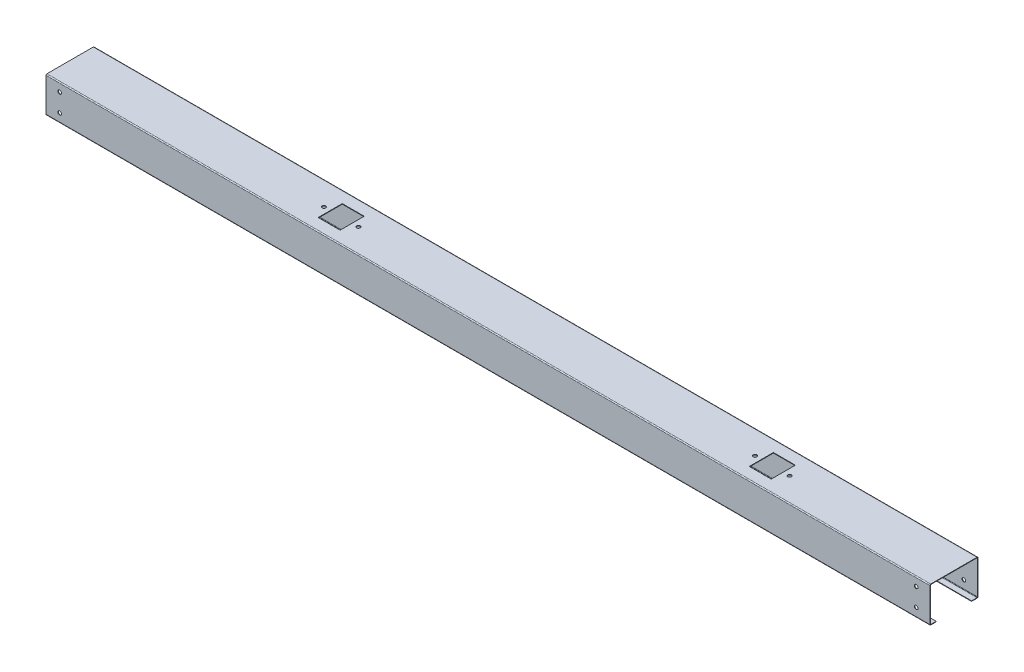
SolidWorks part; units mm, degrees
note: The reader was unsure of these and kept them because the rebuilt part matched: thickness of "Base-Flange1", "Edge-Flange1", "Edge-Flange2", "Sheet-Metal1", "Sheet-Metal2", "Sheet-Metal3", "Sheet-Metal5", "Sheet-Metal15", "Sheet-Metal16", "Sheet-Metal17", "Sheet-Metal18", "Sheet-Metal19"; flange length of "Edge-Flange1", "Edge-Flange2".
ref_plane "Front Plane" through (0, 0, 0) normal (0, 0, 1) x (1, 0, 0)
ref_plane "Top Plane" through (0, 0, 0) normal (0, 1, 0) x (1, 0, 0)
ref_plane "Right Plane" through (0, 0, 0) normal (1, 0, 0) x (0, 0, -1)
sketch "Sketch1" plane through (0, 0, 0) normal (0, 1, 0) x (1, 0, 0)
  line L1 (-698.5, -38.1) -> (698.5, -38.1)
  line L2 (-698.5, -38.1) -> (-698.5, 38.1)
  line L3 (-698.5, 38.1) -> (698.5, 38.1)
  line L4 (698.5, -38.1) -> (698.5, 38.1)
  line L5 (-698.5, -38.1) -> (698.5, 38.1) construction
  line L6 (-698.5, 38.1) -> (698.5, -38.1) construction
  point P0 (0, 0)
  dimension "D1" = 1397
  dimension "D2" = 76.2
base flange "Base-Flange1" sketch "Sketch1" thickness 0.7595 reverse thickness direction no parameters "D1"=0.7366
sketch "Sketch6" plane through (0, 0, 0) normal (0, 1, 0) x (1, 0, 0)
  line L0 (698.5, -38.1) -> (698.5, 38.1) construction
  line L1 (-287.3375, -19.05) -> (-263.7165, -19.05)
  line L2 (-287.3375, -19.05) -> (-287.3375, 19.05)
  line L3 (-287.3375, 19.05) -> (-263.7165, 19.05)
  line L4 (-252.6665, -19.05) -> (-252.6665, 19.05)
  line L5 (-287.3375, -19.05) -> (-252.6665, 19.05) construction
  line L6 (-287.3375, 19.05) -> (-252.6665, -19.05) construction
  line L7 (394.1445, -19.05) -> (417.7655, -19.05)
  line L8 (394.1445, -19.05) -> (394.1445, 19.05)
  line L9 (394.1445, 19.05) -> (417.7655, 19.05)
  line L10 (428.8155, -19.05) -> (428.8155, 19.05)
  line L11 (394.1445, -19.05) -> (428.8155, 19.05) construction
  line L12 (394.1445, 19.05) -> (428.8155, -19.05) construction
  line L13 (-263.7165, 19.05) -> (-252.6665, 19.05)
  line L14 (-263.7165, -19.05) -> (-252.6665, -19.05)
  line L15 (417.7655, 19.05) -> (428.8155, 19.05)
  line L16 (417.7655, -19.05) -> (428.8155, -19.05)
  point P0 (-270.002, 0)
  point P6 (411.48, 0)
  point P12 (0, 0)
  point P15 (0, 0)
  point P17 (-287.3375, 0)
  point P19 (-252.6665, 0)
  point P20 (394.1445, 0)
  point P23 (428.8155, 0)
  dimension "D1" = 34.671
  dimension "D2" = 38.1
  dimension "D3" = 34.671
  dimension "D4" = 38.1
  dimension "D5" = 287.02
  dimension "D6" = 681.482
extrude "Cut-Extrude1" cut sketch "Sketch6" against normal blind 10 normal cut yes
sketch "Sketch7" plane through (0, 0, 0) normal (0, 1, 0) x (1, 0, 0)
  line L0 (-287.3375, 19.05) -> (-287.3375, -19.05) construction
  line L1 (-252.6665, -19.05) -> (-252.6665, 19.05) construction
  line L2 (394.1445, -19.05) -> (394.1445, 19.05) construction
  line L4 (428.8155, -19.05) -> (428.8155, 19.05) construction
  circle A0 centre (-297.3375, 0) radius 2.8194
  circle A1 centre (-242.6665, 0) radius 2.8194
  circle A4 centre (384.1445, 0) radius 2.8194
  circle A5 centre (438.8155, 0) radius 2.8194
  dimension "D1" = 5.6388
  dimension "D2" = 10
  dimension "D4" = 5.6388
  dimension "D8" = 5.6388
  dimension "D9" = 5.6388
  dimension "D3" = 10
  dimension "D5" = 10
  dimension "D7" = 10
extrude "Cut-Extrude2" cut sketch "Sketch7" against normal blind 10 normal cut yes
edge flange "Edge-Flange1" sketch "Sketch37" flange profiles "Sketch37", "Sketch39" flange angle 90 flange length 55.372 flange position material inside bend radius 0.7366 thickness 0.7595 relief rectangular parameters "D6"=10, "D8"=0.254
sketch "Sketch37" plane through (0, -0.7595, -38.1) normal (0, 0, -1) x (1, 0, 0)
  line L0 (698.5, 0) -> (-698.5, 0) construction
  line L1 (698.5, 0) -> (-698.5, 0)
  line L2 (-698.5, 0) -> (-698.5, 54.6125)
  line L3 (-698.5, 54.6125) -> (698.5, 54.6125)
  line L4 (698.5, 54.6125) -> (698.5, 0)
sketch "Sketch39" plane through (0, -0.7595, 38.1) normal (0, 0, 1) x (-1, 0, 0)
  line L0 (698.5, 0) -> (-698.5, 0) construction
  line L1 (698.5, 0) -> (-698.5, 0)
  line L2 (-698.5, 0) -> (-698.5, 54.6125)
  line L3 (-698.5, 54.6125) -> (698.5, 54.6125)
  line L4 (698.5, 54.6125) -> (698.5, 0)
bend "EdgeBend8" bend radius 0.7366 bend angle 90 parameters "D5"=4
bend "EdgeBend9" bend radius 0.7366 bend angle 90 parameters "D5"=5
sketch "Sketch41" plane through (0, 0, -38.1) normal (0, 0, -1) x (-1, 0, 0)
  line L0 (683.16, -13.4595) -> (670.46, -13.4595) construction
  line L1 (683.16, -16.2789) -> (670.46, -16.2789)
  line L2 (683.16, -10.6401) -> (670.46, -10.6401)
  line L3 (698.5, -55.372) -> (698.5, -1.4961) construction
  line L6 (-670.56, -13.448) -> (-683.26, -13.448) construction
  line L7 (-670.56, -16.2674) -> (-683.26, -16.2674)
  line L10 (-670.56, -10.6286) -> (-683.26, -10.6286)
  line L11 (-698.5, 0) -> (-698.5, -1.4961) construction
  line L12 (-698.5, -1.4961) -> (-698.5, -55.372) construction
  arc A0 (683.16, -16.2789) -> (683.16, -10.6401) centre (683.16, -13.4595) ccw
  arc A1 (670.46, -10.6401) -> (670.46, -16.2789) centre (670.46, -13.4595) ccw
  arc A4 (-670.56, -16.2674) -> (-670.56, -10.6286) centre (-670.56, -13.448) ccw
  arc A5 (-683.26, -10.6286) -> (-683.26, -16.2674) centre (-683.26, -13.448) ccw
  point P2 (676.81, -13.4595)
  point P11 (-676.91, -13.448)
  point P21 (-698.5, -0.748)
  dimension "D1" = 5.6388
  dimension "D4" = 12.7
  dimension "D8" = 5.6388
  dimension "D2" = 21.69
  dimension "D3" = 12.7
  dimension "D5" = 12.7
  dimension "D6" = 21.59
  dimension "D7" = 12.7
extrude "Cut-Extrude3" [suppressed] cut sketch "Sketch41" against normal through all both and the other way through all
sketch "Sketch43" plane through (0, 0, -38.1) normal (0, 0, -1) x (-1, 0, 0)
  line L0 (-698.5, -55.372) -> (698.5, -55.372) construction
  line L1 (698.5, -55.372) -> (698.5, -1.4961) construction
  circle A0 centre (-228.5689, -30.4791) radius 2.8194
  circle A1 centre (-177.8, -28.702) radius 2.8194
  dimension "D4" = 5.6388
  dimension "D1" = 26.67
  dimension "D2" = 876.3
  dimension "D3" = 50.8
extrude "Cut-Extrude4" [suppressed] cut sketch "Sketch43" against normal up to next
sketch "Sketch44" plane through (0, 0, -38.1) normal (0, 0, -1) x (-1, 0, 0)
  line L0 (-698.5, -1.4961) -> (-698.5, -55.372) construction
  line L1 (698.5, -55.372) -> (698.5, -1.4961) construction
  line L2 (-698.5, -55.372) -> (698.5, -55.372) construction
  circle A0 centre (-676.91, -13.4595) radius 2.8194
  circle A1 centre (676.91, -13.4595) radius 2.8194
  circle A2 centre (-676.91, -42.164) radius 2.8194
  circle A3 centre (676.91, -42.164) radius 2.8194
  dimension "D3" = 5.6388
  dimension "D6" = 5.6388
  dimension "D9" = 21.59
  dimension "D1" = 21.59
  dimension "D2" = 12.7
  dimension "D4" = 21.59
  dimension "D5" = 12.7
  dimension "D7" = 13.208
  dimension "D8" = 21.59
  dimension "D10" = 13.208
extrude "Cut-Extrude5" cut sketch "Sketch44" against normal through all both and the other way through all normal cut yes
edge flange "Edge-Flange2" sketch "Sketch47" flange profiles "Sketch47", "Sketch49" flange angle 90 flange length 10.16 flange position material outside bend radius 0.7366 thickness 0.7595 relief rectangular parameters "D6"=10, "D8"=0.254
sketch "Sketch47" plane through (0, -55.372, 37.3405) normal (0, 1, 0) x (1, 0, 0)
  line L2 (-698.5, 0) -> (-698.5, 9.4005)
  line L3 (-698.5, 9.4005) -> (698.5, 9.4005)
  line L4 (698.5, 9.4005) -> (698.5, 0)
  line L5 (698.5, 0) -> (-698.5, 0) construction
  line L6 (698.5, 0) -> (-698.5, 0)
sketch "Sketch49" plane through (0, -55.372, -37.3405) normal (0, 1, 0) x (-1, 0, 0)
  line L0 (698.5, 0) -> (-698.5, 0) construction
  line L1 (698.5, 0) -> (-698.5, 0)
  line L2 (698.5, 0) -> (698.5, 9.4005)
  line L3 (698.5, 9.4005) -> (-698.5, 9.4005)
  line L4 (-698.5, 9.4005) -> (-698.5, 0)
bend "EdgeBend10" bend radius 0.7366 bend angle 90 parameters "D5"=6
bend "EdgeBend11" bend radius 0.7366 bend angle 90 parameters "D5"=8
sketch "Sketch50" plane through (0, -56.1315, 0) normal (0, -1, 0) x (1, 0, 0)
  line L0 (698.5, 36.6039) -> (698.5, 27.94) construction
  line L1 (698.5, 36.6039) -> (-698.5, 36.6039) construction
  line L2 (698.5, -36.6039) -> (-698.5, -36.6039) construction
  circle A0 centre (623.57, 32.7939) radius 1.651
  circle A1 centre (623.57, -32.7939) radius 1.651
  circle A2 centre (127, -32.7939) radius 1.651
  circle A3 centre (127, 32.7939) radius 1.651
  circle A4 centre (-313.69, 32.7939) radius 1.651
  circle A5 centre (-313.69, -32.7939) radius 1.651
  circle A6 centre (-542.29, 32.7939) radius 1.651
  circle A7 centre (-542.29, -32.7939) radius 1.651
  circle A8 centre (-656.59, 32.7939) radius 1.651
  circle A9 centre (-656.59, -32.7939) radius 1.651
  circle A10 centre (318.77, 32.7939) radius 1.651
  circle A11 centre (318.77, -32.7939) radius 1.651
  dimension "D1" = 3.302
  dimension "D2" = 74.93
  dimension "D3" = 3.81
  dimension "D4" = 3.81
  dimension "D5" = 496.57
  dimension "D6" = 440.69
  dimension "D7" = 228.6
  dimension "D8" = 114.3
  dimension "D9" = 304.8
extrude "Cut-Extrude6" cut sketch "Sketch50" against normal up to next normal cut yes
sketch "Bend-Lines1" [suppressed] plane through (0, 0, 0) normal (0, 1, 0) x (1, 0, 0)
sketch "Bounding-Box1" [suppressed] plane through (0, 0, 0) normal (0, 1, 0) x (1, 0, 0)
sheet metal parameters "Sheet-Metal1" thickness 0.7595 parameters "D1"=0.7366
flat pattern "Flat-Pattern1" [suppressed]
sketch "Bend-Lines2" plane through (0, 0, 0) normal (0, 1, 0) x (1, 0, 0)
sketch3d "Bounding-Box2" [suppressed]
  line L0 (50.8, 38.1, 0) -> (-50.8, 38.1, 0) construction
  line L1 (50.8, -38.1, 0) -> (-50.8, -38.1, 0) construction
  line L2 (50.8, 38.1, 0) -> (50.8, -38.1, 0) construction
  line L3 (-50.8, 38.1, 0) -> (-50.8, -38.1, 0) construction
sheet metal parameters "Sheet-Metal2" thickness 0.7595 parameters "D1"=0.7366, "D7"=1.7366
flat pattern "Flat-Pattern1"
sketch "Bend-Lines2" plane through (0, 0, 0) normal (0, 1, 0) x (1, 0, 0)
sketch3d "Bounding-Box2" [suppressed]
  line L0 (571.5, 38.1, 0) -> (-571.5, 38.1, 0) construction
  line L1 (571.5, -38.1, 0) -> (-571.5, -38.1, 0) construction
  line L2 (571.5, 38.1, 0) -> (571.5, -38.1, 0) construction
  line L3 (-571.5, 38.1, 0) -> (-571.5, -38.1, 0) construction
sheet metal parameters "Sheet-Metal3" thickness 0.7595 parameters "D1"=0.7366, "D7"=1.7366
flat pattern "Flat-Pattern1"
sketch "Bend-Lines2" plane through (0, 0, 0) normal (0, 1, 0) x (1, 0, 0)
sketch3d "Bounding-Box2" [suppressed]
  line L0 (571.5, 31.75, 0) -> (-571.5, 31.75, 0) construction
  line L1 (571.5, -31.75, 0) -> (-571.5, -31.75, 0) construction
  line L2 (571.5, 31.75, 0) -> (571.5, -31.75, 0) construction
  line L3 (-571.5, 31.75, 0) -> (-571.5, -31.75, 0) construction
sheet metal parameters "Sheet-Metal5" thickness 0.7595 parameters "D1"=0.7366, "D7"=1.7366
flat pattern "Flat-Pattern1"
sketch "Bend-Lines2" plane through (0, 0, 0) normal (0, 1, 0) x (1, 0, 0)
  line L2 (-698.5, -37.4807) -> (698.5, -37.4807) construction
  line L3 (698.5, 37.4807) -> (-698.5, 37.4807) construction
  line L5 (-698.5, -37.4807) -> (698.5, -37.4807) construction
  line L6 (698.5, 37.4807) -> (-698.5, 37.4807) construction
  point P0 (697.8807, -37.1609)
  point P1 (697.8807, 37.1609)
sketch3d "Bounding-Box2" [suppressed]
  line L0 (698.5, 94.0114, 0) -> (-698.5, 94.0114, 0) construction
  line L1 (698.5, -94.0114, 0) -> (-698.5, -94.0114, 0) construction
  line L2 (698.5, 94.0114, 0) -> (698.5, -94.0114, 0) construction
  line L3 (-698.5, 94.0114, 0) -> (-698.5, -94.0114, 0) construction
bend of the flat pattern "Flatten-<EdgeBend8>1"
bend of the flat pattern "Flatten-<EdgeBend9>1"
sheet metal parameters "Sheet-Metal15" thickness 0.7595 parameters "D1"=0.7366, "D7"=1.7366
flat pattern "Flat-Pattern1"
sketch "Bend-Lines2" plane through (0, 0, 0) normal (0, 1, 0) x (1, 0, 0)
  line L2 (-698.5, -37.4807) -> (698.5, -37.4807) construction
  line L3 (698.5, 37.4807) -> (-698.5, 37.4807) construction
  line L5 (-698.5, -37.4807) -> (698.5, -37.4807) construction
  line L6 (698.5, 37.4807) -> (-698.5, 37.4807) construction
sketch3d "Bounding-Box2" [suppressed]
  line L0 (698.5, 94.0114, 0) -> (-698.5, 94.0114, 0) construction
  line L1 (698.5, -94.0114, 0) -> (-698.5, -94.0114, 0) construction
  line L2 (698.5, 94.0114, 0) -> (698.5, -94.0114, 0) construction
  line L3 (-698.5, 94.0114, 0) -> (-698.5, -94.0114, 0) construction
bend of the flat pattern "Flatten-<EdgeBend8>1"
bend of the flat pattern "Flatten-<EdgeBend9>1"
sheet metal parameters "Sheet-Metal16" thickness 0.7595 parameters "D1"=0.7366, "D7"=1.7366
flat pattern "Flat-Pattern1"
sketch "Bend-Lines2" plane through (0, 0, 0) normal (0, 1, 0) x (1, 0, 0)
  line L2 (-698.5, -37.4807) -> (698.5, -37.4807) construction
  line L3 (698.5, 37.4807) -> (-698.5, 37.4807) construction
  line L5 (-698.5, -37.4807) -> (698.5, -37.4807) construction
  line L6 (698.5, 37.4807) -> (-698.5, 37.4807) construction
sketch3d "Bounding-Box2" [suppressed]
  line L0 (698.5, 94.0114, 0) -> (-698.5, 94.0114, 0) construction
  line L1 (698.5, -94.0114, 0) -> (-698.5, -94.0114, 0) construction
  line L2 (698.5, 94.0114, 0) -> (698.5, -94.0114, 0) construction
  line L3 (-698.5, 94.0114, 0) -> (-698.5, -94.0114, 0) construction
bend of the flat pattern "Flatten-<EdgeBend8>1"
bend of the flat pattern "Flatten-<EdgeBend9>1"
sheet metal parameters "Sheet-Metal17" thickness 0.7595 parameters "D1"=0.7366, "D7"=1.7366
flat pattern "Flat-Pattern1"
sketch "Bend-Lines2" plane through (0, 0, 0) normal (0, 1, 0) x (1, 0, 0)
  line L0 (698.5, 93.6436) -> (-698.5, 93.6436) construction
  line L1 (-698.5, -93.6436) -> (698.5, -93.6436) construction
  line L2 (-698.5, -37.4807) -> (698.5, -37.4807) construction
  line L3 (698.5, 37.4807) -> (-698.5, 37.4807) construction
  line L4 (698.5, 93.6436) -> (-698.5, 93.6436) construction
  line L5 (-698.5, -37.4807) -> (698.5, -37.4807) construction
  line L6 (698.5, 37.4807) -> (-698.5, 37.4807) construction
  line L7 (-698.5, -93.6436) -> (698.5, -93.6436) construction
sketch3d "Bounding-Box2" [suppressed]
  line L0 (698.5, 103.1843, 0) -> (-698.5, 103.1843, 0) construction
  line L1 (698.5, -103.1843, 0) -> (-698.5, -103.1843, 0) construction
  line L2 (698.5, 103.1843, 0) -> (698.5, -103.1843, 0) construction
  line L3 (-698.5, 103.1843, 0) -> (-698.5, -103.1843, 0) construction
bend of the flat pattern "Flatten-<EdgeBend8>1"
bend of the flat pattern "Flatten-<EdgeBend9>1"
sheet metal parameters "Sheet-Metal18" thickness 0.7595 parameters "D1"=0.7366, "D7"=1.7366
flat pattern "Flat-Pattern1"
sketch "Bend-Lines2" plane through (0, 0, 0) normal (0, 1, 0) x (1, 0, 0)
  line L0 (-698.5, -93.6436) -> (698.5, -93.6436) construction
  line L1 (-698.5, -93.6436) -> (698.5, -93.6436) construction
  line L2 (-698.5, -37.4807) -> (698.5, -37.4807) construction
  line L3 (698.5, 37.4807) -> (-698.5, 37.4807) construction
  line L4 (698.5, 93.6436) -> (-698.5, 93.6436) construction
  line L5 (-698.5, -37.4807) -> (698.5, -37.4807) construction
  line L6 (698.5, 37.4807) -> (-698.5, 37.4807) construction
  line L7 (698.5, 93.6436) -> (-698.5, 93.6436) construction
sketch3d "Bounding-Box2" [suppressed]
  line L0 (698.5, 103.1843, 0) -> (-698.5, 103.1843, 0) construction
  line L1 (698.5, -103.1843, 0) -> (-698.5, -103.1843, 0) construction
  line L2 (698.5, 103.1843, 0) -> (698.5, -103.1843, 0) construction
  line L3 (-698.5, 103.1843, 0) -> (-698.5, -103.1843, 0) construction
bend of the flat pattern "Flatten-<EdgeBend8>1"
bend of the flat pattern "Flatten-<EdgeBend9>1"
bend of the flat pattern "Flatten-<EdgeBend10>1"
bend of the flat pattern "Flatten-<EdgeBend11>1"
sheet metal parameters "Sheet-Metal19" thickness 0.7595 parameters "D1"=0.7366, "D7"=1.7366
flat pattern "Flat-Pattern1"
sketch "Bend-Lines2" plane through (0, 0, 0) normal (0, 1, 0) x (1, 0, 0)
  line L0 (-698.5, -92.3736) -> (698.5, -92.3736) construction
  line L1 (-698.5, -92.3736) -> (698.5, -92.3736) construction
  line L2 (-698.5, -37.4807) -> (698.5, -37.4807) construction
  line L3 (698.5, 37.4807) -> (-698.5, 37.4807) construction
  line L4 (698.5, 92.3736) -> (-698.5, 92.3736) construction
  line L5 (-698.5, -37.4807) -> (698.5, -37.4807) construction
  line L6 (698.5, 37.4807) -> (-698.5, 37.4807) construction
  line L7 (698.5, 92.3736) -> (-698.5, 92.3736) construction
sketch3d "Bounding-Box2" [suppressed]
  line L0 (698.5, 101.9143, 0) -> (-698.5, 101.9143, 0) construction
  line L1 (698.5, -101.9143, 0) -> (-698.5, -101.9143, 0) construction
  line L2 (698.5, 101.9143, 0) -> (698.5, -101.9143, 0) construction
  line L3 (-698.5, 101.9143, 0) -> (-698.5, -101.9143, 0) construction
bend of the flat pattern "Flatten-<EdgeBend8>1"
bend of the flat pattern "Flatten-<EdgeBend9>1"
bend of the flat pattern "Flatten-<EdgeBend10>1"
bend of the flat pattern "Flatten-<EdgeBend11>1"
